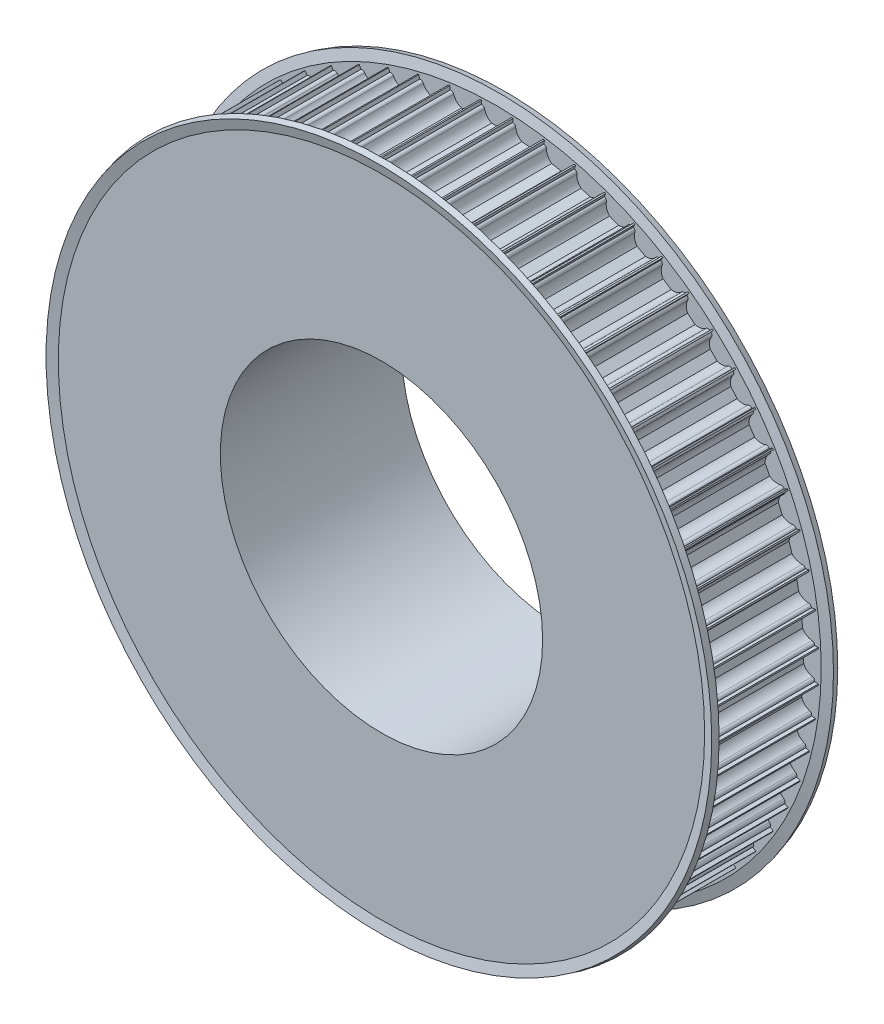
SolidWorks part; units mm, degrees
ref_plane "Front Plane" through (0, 0, 0) normal (0, 0, 1) x (1, 0, 0)
ref_plane "Top Plane" through (0, 0, 0) normal (0, 1, 0) x (1, 0, 0)
ref_plane "Right Plane" through (0, 0, 0) normal (1, 0, 0) x (0, 0, -1)
sketch "Sketch1" plane through (0, 0, 0) normal (1, 0, 0) x (0, 0, -1)
  line L0 (0, 0) -> (37.7091, 0) construction
  line L1 (0, 40) -> (0, 80)
  line L2 (0, 80) -> (30, 80)
  line L3 (30, 80) -> (30, 55.5)
  line L4 (30, 55.5) -> (45, 55.5)
  line L5 (45, 55.5) -> (45, 40)
  line L6 (45, 40) -> (0, 40)
  dimension "D1" = 80
  dimension "D2" = 40
  dimension "D3" = 30
  dimension "D4" = 15
  dimension "D5" = 15.5
revolve "Revolve1" add sketch "Sketch1" angle 360 about L0
sketch "Sketch2" plane through (0, 0, 0) normal (0, 0, 1) x (1, 0, 0)
  line L0 (-3.6742, 79) -> (-3.75, 79)
  line L1 (-3.75, 79) -> (-3.75, 81)
  line L2 (-3.75, 81) -> (3.75, 81)
  line L3 (3.75, 81) -> (3.75, 79)
  line L4 (3.75, 79) -> (3.6742, 79)
  line L5 (-1.199, 76.25) -> (1.199, 76.25)
  arc A0 (2.9394, 78.4) -> (1.199, 76.25) centre (0, 79) cw
  arc A1 (2.9394, 78.4) -> (3.6742, 79) centre (3.6742, 78.25) cw
  arc A2 (-2.9394, 78.4) -> (-3.6742, 79) centre (-3.6742, 78.25) ccw
  arc A3 (-1.199, 76.25) -> (-2.9394, 78.4) centre (0, 79) cw
  dimension "D1" = 3
  dimension "D5" = 0.75
  dimension "D2" = 79
  dimension "D3" = 7.5
  dimension "D4" = 2
  dimension "D6" = 2.75
extrude "Cut-Extrude1" cut sketch "Sketch2" against normal up to next
pattern_circular "CirPattern1" count 64 over 360 about axis through (0, 0, 0) along (0, 0, 1) of "Cut-Extrude1"
sketch "Sketch3" plane through (0, 0, 0) normal (1, 0, 0) x (0, 0, -1)
  line L0 (15, -40.9775) -> (15, -16.0516) construction
  line L1 (30, -40.9775) -> (0, -40.9775) construction
  line L2 (30, -16.0516) -> (0, -16.0516) construction
  line L3 (30, 55.5) -> (30, 80.2218)
  line L4 (30, 80.2218) -> (30.6431, 82.6218)
  line L5 (30.6431, 82.6218) -> (29.1942, 83.01)
  line L6 (29.1942, 83.01) -> (28.5511, 80.61)
  line L7 (28.5511, 80.61) -> (28.5511, 55.5)
  line L8 (28.5511, 55.5) -> (30, 55.5)
  line L9 (1.4489, 55.5) -> (0, 55.5)
  line L10 (0, 55.5) -> (0, 80.2218)
  line L11 (0, 80.2218) -> (-0.6431, 82.6218)
  line L12 (-0.6431, 82.6218) -> (0.8058, 83.01)
  line L13 (0.8058, 83.01) -> (1.4489, 80.61)
  line L14 (1.4489, 80.61) -> (1.4489, 55.5)
  line L15 (0, 0) -> (26.6899, 0) construction
  dimension "D1" = 15
  dimension "D2" = 1.5
  dimension "D3" = 25.11
  dimension "D4" = 2.4
revolve "Revolve2" add sketch "Sketch3" angle 360 about L15
